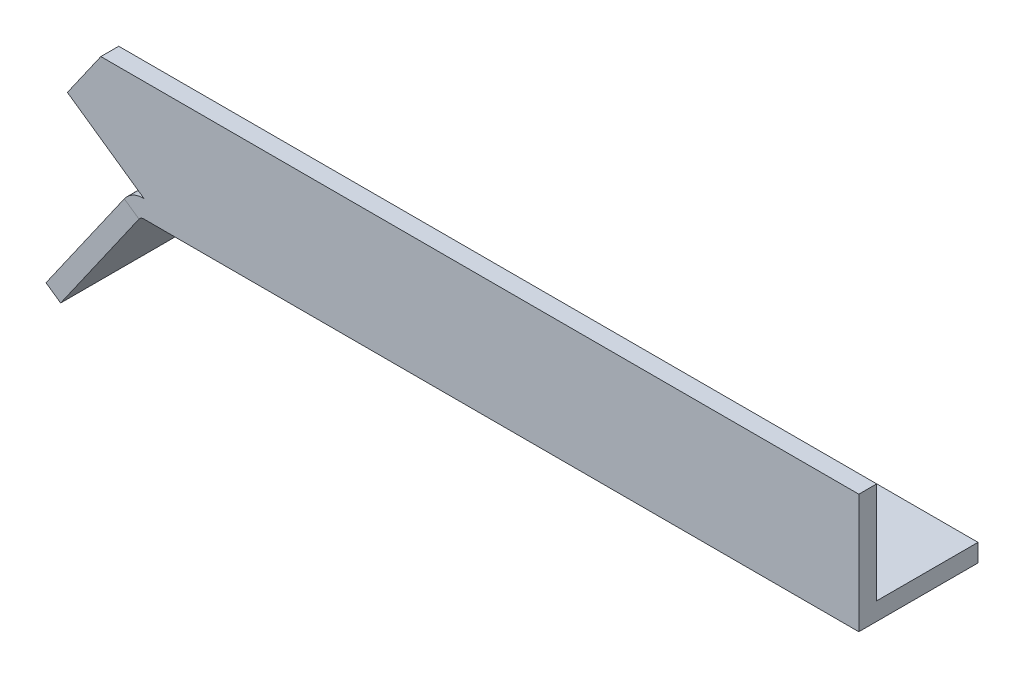
SolidWorks part; units mm, degrees
note: The reader was unsure of these and kept them because the rebuilt part matched: flange length of "Ребро-кромка1".
ref_plane "Спереди" through (0, 0, 0) normal (0, 0, 1) x (1, 0, 0)
ref_plane "Сверху" through (0, 0, 0) normal (0, 1, 0) x (1, 0, 0)
ref_plane "Справа" through (0, 0, 0) normal (1, 0, 0) x (0, 0, -1)
sketch "Эскиз1" plane through (0, 0, 0) normal (1, 0, 0) x (0, 0, -1)
  line L0 (0, 20) -> (0, 0)
  line L1 (0, 0) -> (20, 0)
extrude "Вытянуть-Тонкостенный1" add sketch "Эскиз1" along normal blind 120 thin thin type one direction reverse wall 3
sketch "Эскиз3" plane through (0, 0, 0) normal (0, -1, 0) x (1, 0, 0)
  line L1 (0, 0) -> (120, 0)
  line L2 (0, 0) -> (0, -20)
  line L3 (0, -20) -> (120, -20)
  line L4 (120, 0) -> (120, -20)
base flange "Базовая кромка1" sketch "Эскиз3" thickness 3 reverse thickness direction no parameters "D1"=3
edge flange "Ребро-кромка1" sketch "Эскиз10" flange angle 125 flange length 25 flange position bend outside bend radius 1 thickness 3 parameters "D6"=10
sketch "Эскиз10" plane through (0, 0, 0) normal (0.8192, -0.5736, 0) x (0, 0, 1)
  line L2 (-20, 0) -> (-20, 23.4383)
  line L3 (-20, 23.4383) -> (0, 23.4383)
  line L4 (0, 23.4383) -> (0, 0)
  line L9 (0, 0) -> (-20, 0) construction
  line L10 (0, 0) -> (-20, 0)
bend "EdgeBend1" bend radius 1 bend angle 55 parameters "D5"=1
sketch "Эскиз11" plane through (0, 0, 0) normal (0, 0, 1) x (1, 0, 0)
  line L0 (0, 20) -> (0, 3)
  line L2 (-7.2165, 20) -> (0, 20)
  line L3 (0, 3) -> (-12.8297, 11.9835)
  line L4 (-12.8297, 11.9835) -> (-7.2165, 20)
extrude "Бобышка-Вытянуть1" add sketch "Эскиз11" against normal blind 3
unfold "Разогнуть1" [suppressed]
sketch "Сгиб-Линии1" [suppressed] plane through (0, 0, 0) normal (0, 1, 0) x (1, 0, 0)
sketch "Граничная рамка1" [suppressed] plane through (0, 0, 0) normal (0, 1, 0) x (1, 0, 0)
sheet metal parameters "Листовой металл2" thickness 3 parameters "D1"=3
flat pattern "Развертка2"
sketch "Сгиб-Линии2" plane through (0, 0, 0) normal (0, 1, 0) x (1, 0, 0)
sketch3d "Граничная рамка2" [suppressed]
  line L0 (140, 20, 0) -> (0, 20, 0) construction
  line L1 (140, 0, 0) -> (0, 0, 0) construction
  line L2 (140, 20, 0) -> (140, 0, 0) construction
  line L3 (0, 20, 0) -> (0, 0, 0) construction
sheet metal parameters "Листовой металл3" thickness 3 parameters "D1"=3
flat pattern "Развертка2"
sketch "Сгиб-Линии2" plane through (0, 0, 0) normal (0, -1, 0) x (-1, 0, 0)
  line L0 (1.9199, 20) -> (1.9199, 0) construction
  line L1 (1.9199, 20) -> (1.9199, 0) construction
sketch3d "Граничная рамка2" [suppressed]
  line L0 (-140, 20, 0) -> (24.7575, 20, 0) construction
  line L1 (-140, 0, 0) -> (24.7575, 0, 0) construction
  line L2 (-140, 20, 0) -> (-140, 0, 0) construction
  line L3 (24.7575, 20, 0) -> (24.7575, 0, 0) construction
bend of the flat pattern "Плоское состояние-<EdgeBend1>1"
sheet metal parameters "Листовой металл4" thickness 3 parameters "D1"=3
flat pattern "Развертка2"
sketch "Сгиб-Линии2" plane through (-2.8068, 1.9653, 0) normal (-0.8192, 0.5736, 0) x (0, 0, 1)
  line L0 (0, 1.1007) -> (-20, 1.1007) construction
  line L1 (0, 1.1007) -> (-20, 1.1007) construction
sketch3d "Граничная рамка2" [suppressed]
  line L0 (-20, 123.3192, 0) -> (-20, -23.4383, 0) construction
  line L1 (0, 123.3192, 0) -> (0, -23.4383, 0) construction
  line L2 (-20, 123.3192, 0) -> (0, 123.3192, 0) construction
  line L3 (-20, -23.4383, 0) -> (0, -23.4383, 0) construction
bend of the flat pattern "Плоское состояние-<EdgeBend1>1"
